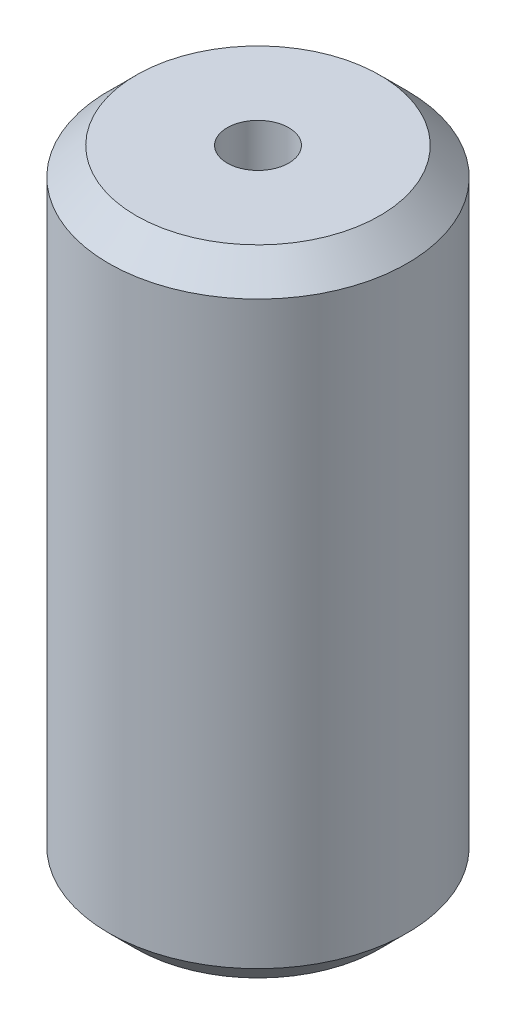
SolidWorks part; units mm, degrees
ref_plane "Front Plane" through (0, 0, 0) normal (0, 0, 1) x (1, 0, 0)
ref_plane "Top Plane" through (0, 0, 0) normal (0, 1, 0) x (1, 0, 0)
ref_plane "Right Plane" through (0, 0, 0) normal (1, 0, 0) x (0, 0, -1)
sketch "Sketch1" plane through (0, 0, 0) normal (0, 1, 0) x (1, 0, 0)
  circle A0 centre (0, 0) radius 5
  dimension "SHAFT_OD" = 10
extrude "Boss-Extrude1" add sketch "Sketch1" along normal blind 21.2566
sketch "Sketch2" plane through (0, 0, 0) normal (0, 1, 0) x (1, 0, 0)
  circle A0 centre (0, 0) radius 1.0291
  dimension "BORE_D" = 2.0583
extrude "Cut-Extrude1" cut sketch "Sketch2" along normal through all
chamfer "Chamfer1" distance 0.9213 angle 45 2 edges at (0, 21.2566, 5) (0, 0, 5)
